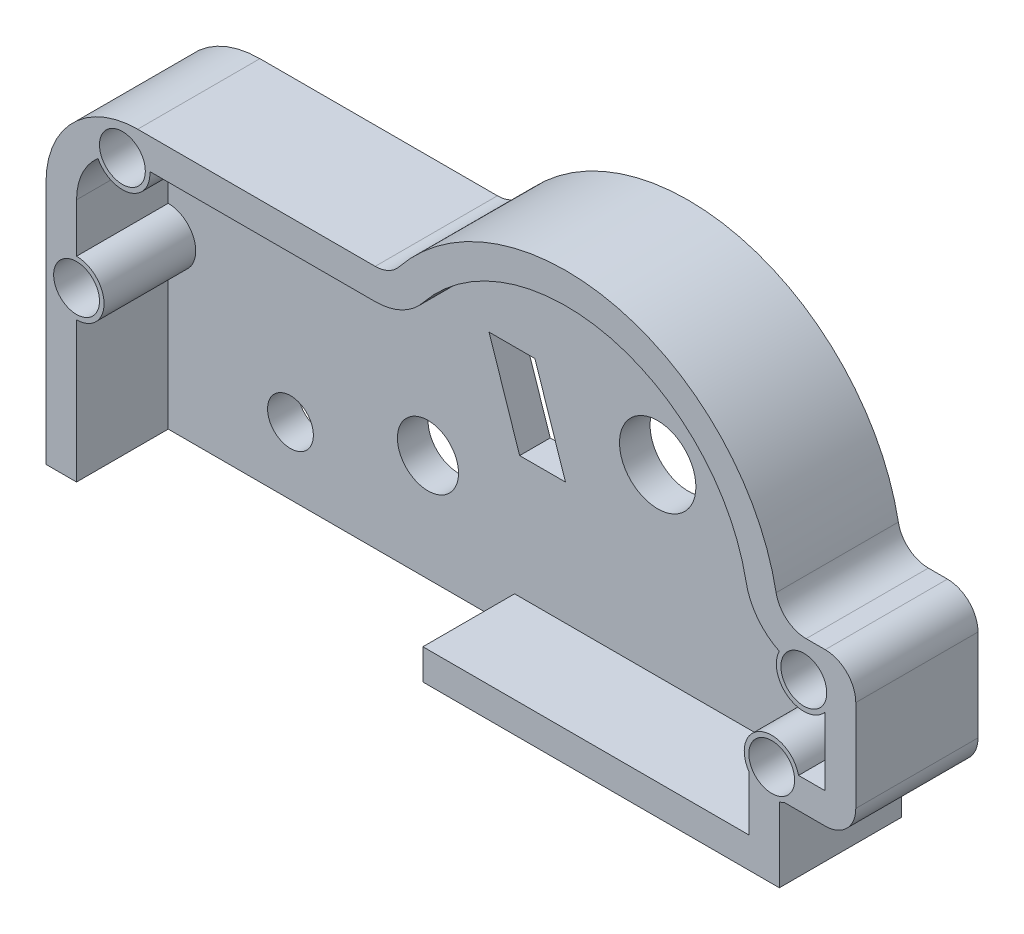
SolidWorks part; units mm, degrees
ref_plane "Front Plane" through (0, 0, 0) normal (0, 0, 1) x (1, 0, 0)
ref_plane "Top Plane" through (0, 0, 0) normal (0, 1, 0) x (1, 0, 0)
ref_plane "Right Plane" through (0, 0, 0) normal (1, 0, 0) x (0, 0, -1)
sketch "Sketch1" plane through (0, 0, 0) normal (0, 0, 1) x (1, 0, 0)
  line L0 (-17.0179, -7) -> (6.9821, -7)
  line L1 (-17.0179, -7) -> (-17.0179, 1)
  line L2 (-14.0179, 4) -> (-6.245, 4)
  line L3 (6.9821, -7) -> (6.9821, -5.5)
  line L4 (7.9821, -4.5) -> (8.4821, -4.5)
  line L5 (9.4821, -3.5) -> (9.4821, -0.5)
  line L6 (8.4821, 0.5) -> (7.8581, 0.5)
  line L7 (6.9821, -5.5) -> (6.9821, -4.5)
  line L8 (6.9821, -4.5) -> (7.9821, -4.5)
  arc A0 (-14.0179, 4) -> (-17.0179, 1) centre (-14.0179, 1) ccw
  arc A1 (6.8759, 1.3125) -> (-5.4644, 4.375) centre (0, 0) ccw
  arc A2 (9.4821, -0.5) -> (8.4821, 0.5) centre (8.4821, -0.5) ccw
  arc A3 (8.4821, -4.5) -> (9.4821, -3.5) centre (8.4821, -3.5) ccw
  arc A5 (-6.245, 4) -> (-5.4644, 4.375) centre (-6.245, 5) ccw
  arc A6 (6.8759, 1.3125) -> (7.8581, 0.5) centre (7.8581, 1.5) ccw
  point P8 (-17.0179, 4)
  point P15 (9.4821, 0.5)
  point P18 (9.4821, -4.5)
  point P21 (6.9821, -4.5)
  point P26 (6.9821, 0.5)
  dimension "D4" = 3
  dimension "D5" = 14
  dimension "D10" = 1
  dimension "D1" = 7
  dimension "D2" = 24
  dimension "D3" = 11
  dimension "D6" = 2.5
  dimension "D7" = 2.5
  dimension "D8" = 5
  dimension "D9" = 2.5
extrude "Boss-Extrude1" add sketch "Sketch1" along normal blind 4
shell "Shell1" thickness 1 removed face at (-5.0179, -7, 2) removed face at (0.4256, -0.539, 4)
sketch "Sketch2" plane through (0, 0, 1) normal (0, 0, 1) x (1, 0, 0)
  line L0 (-5.5179, 1) -> (-4.0179, 1)
  line L1 (-5.5179, 1) -> (-4.5179, -2)
  line L2 (-4.0179, 1) -> (-3.0179, -2)
  line L3 (-4.5179, -2) -> (-3.0179, -2)
  line L4 (-16.0179, -7) -> (5.9821, -7) construction
  line L5 (-17.0179, 1) -> (-17.0179, -7) construction
  line L6 (9.4821, -3.5) -> (9.4821, -0.5) construction
  line L7 (-6.245, 4) -> (-14.0179, 4) construction
  circle A0 centre (0, 0) radius 1.25
  circle A1 centre (-12.0179, -4.8) radius 0.75
  circle A2 centre (-7.5179, -3.5) radius 1
  dimension "D1" = 2.5
  dimension "D2" = 2
  dimension "D4" = 9.5
  dimension "D5" = 1.5
  dimension "D3" = 3.5
  dimension "D6" = 2.2
  dimension "D7" = 5
  dimension "D8" = 13.5
  dimension "D9" = 1.5
  dimension "D10" = 3
  dimension "D11" = 12.5
  dimension "D12" = 3
extrude "Cut-Extrude1" cut sketch "Sketch2" against normal blind 10
sketch "Sketch3" plane through (0, -7, 0) normal (0, -1, 0) x (1, 0, 0)
  line L1 (5.9821, 4) -> (-4.6837, 4)
  line L2 (5.9821, 4) -> (5.9821, 1)
  line L3 (5.9821, 1) -> (-4.6837, 1)
  line L4 (-4.6837, 4) -> (-4.6837, 1)
extrude "Boss-Extrude2" add sketch "Sketch3" against normal blind 1
sketch "Sketch4" plane through (0, 0, 1) normal (0, 0, 1) x (1, 0, 0)
  line L0 (-16.0179, 1) -> (-16.0179, -7) construction
  line L1 (-17.0179, 1) -> (-17.0179, -7) construction
  line L2 (-16.0179, -7) -> (-4.6837, -7) construction
  line L3 (9.4821, -3.5) -> (9.4821, -0.5) construction
  line L4 (-4.6837, -7) -> (6.9821, -7) construction
  line L9 (8.4821, 0.5) -> (7.8581, 0.5) construction
  circle A0 centre (-14.5179, 2.9365) radius 0.9
  arc A1 (-14.0179, 3) -> (-16.0179, 1) centre (-14.0179, 1) ccw construction
  circle A2 centre (-16.0179, -1.5) radius 0.9
  circle A3 centre (7.7821, -0.7) radius 0.9
  circle A4 centre (6.7321, -3.7) radius 0.9
  dimension "D1" = 1.8
  dimension "D6" = 2.75
  dimension "D2" = 2.5
  dimension "D3" = 5.5
  dimension "D4" = 1.7
  dimension "D5" = 1.2
  dimension "D7" = 3.3
extrude "Boss-Extrude3" add sketch "Sketch4" along normal up to surface (3 mm away) up to face at (-0.6891, -0.9947, 4)
sketch "Sketch5" plane through (0, 0, 4) normal (0, 0, 1) x (1, 0, 0)
  circle A0 centre (-14.5179, 2.9365) radius 0.75
  circle A1 centre (-16.0179, -1.5) radius 0.75
  circle A2 centre (6.7321, -3.7) radius 0.75
  circle A3 centre (7.7821, -0.7) radius 0.75
  dimension "D1" = 1.5
extrude "Cut-Extrude2" cut sketch "Sketch5" against normal blind 3
